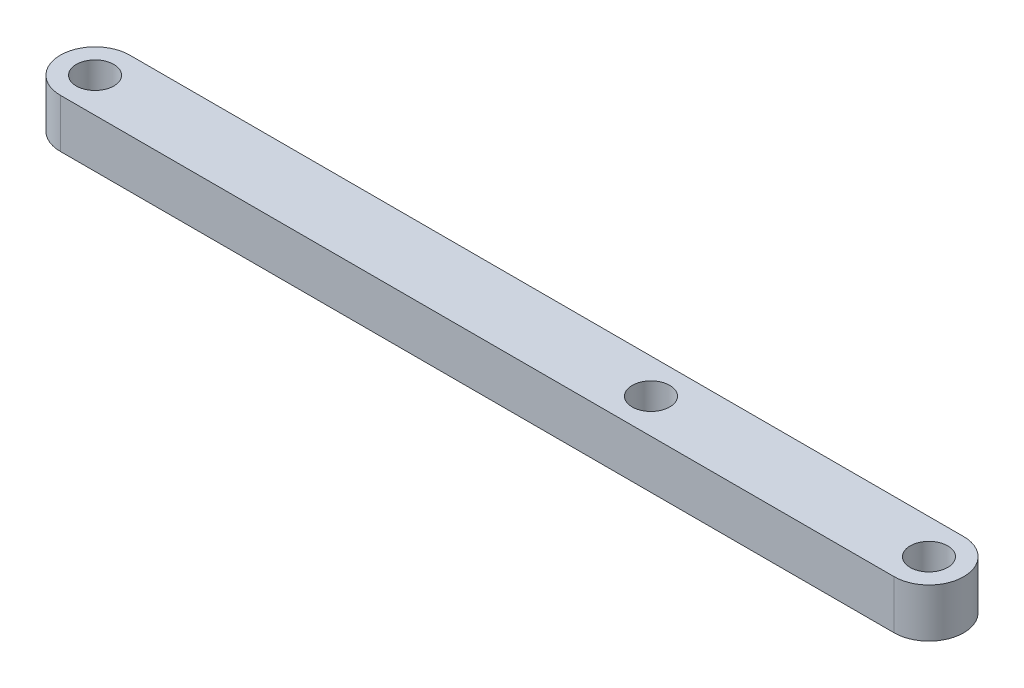
SolidWorks part; units mm, degrees
ref_plane "Front Plane" through (0, 0, 0) normal (0, 0, 1) x (1, 0, 0)
ref_plane "Top Plane" through (0, 0, 0) normal (0, 1, 0) x (1, 0, 0)
ref_plane "Right Plane" through (0, 0, 0) normal (1, 0, 0) x (0, 0, -1)
sketch "Sketch1" plane through (0, 0, 0) normal (0, 1, 0) x (1, 0, 0)
  line L0 (-60, 0) -> (60, 0) construction
  line L1 (-60, -5) -> (60, -5)
  line L3 (-60, 5) -> (60, 5)
  arc A0 (60, 5) -> (60, -5) centre (60, 0) cw
  arc A1 (-60, 5) -> (-60, -5) centre (-60, 0) ccw
  circle A2 centre (-60, 0) radius 2.7
  circle A3 centre (60, 0) radius 2.7
  circle A4 centre (20, 0) radius 2.7
  point P0 (0, 0)
  dimension "D3" = 5.4
  dimension "D4" = 5.4
  dimension "D5" = 5.4
  dimension "D1" = 120
  dimension "D2" = 10
  dimension "D6" = 60
  dimension "D7" = 40
extrude "Boss-Extrude1" add sketch "Sketch1" along normal blind 7
